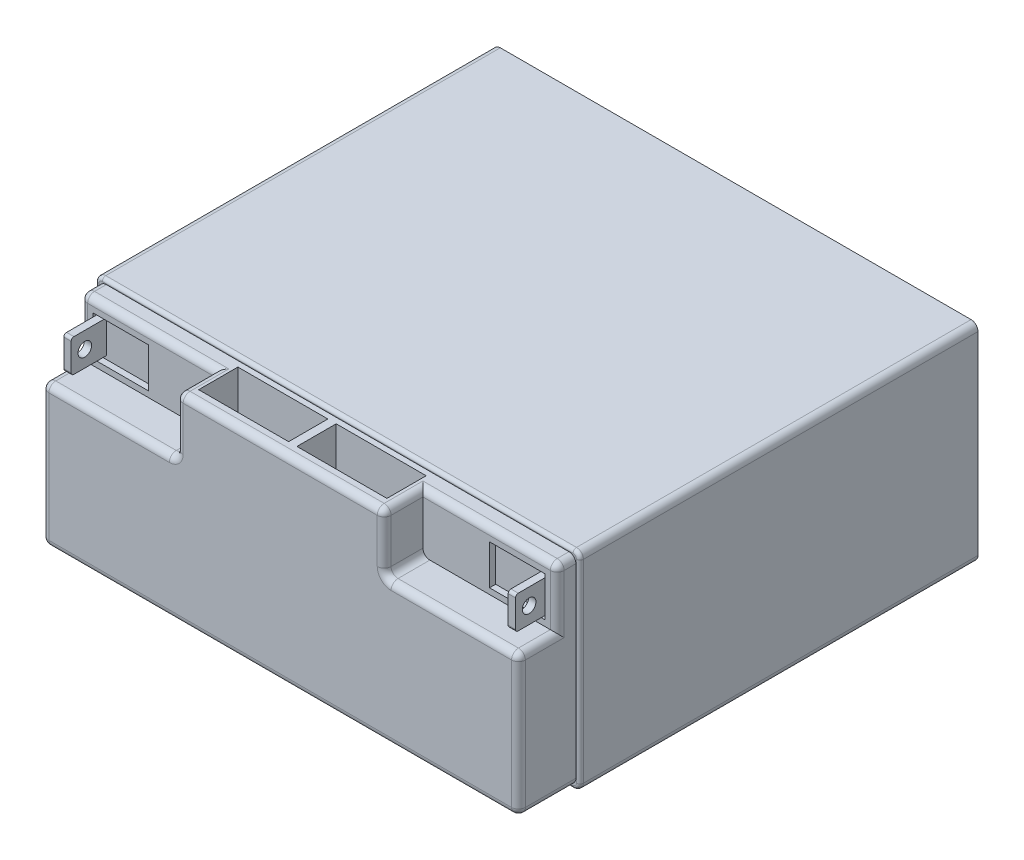
SolidWorks part; units mm, degrees
ref_plane "Front Plane" through (0, 0, 0) normal (0, 0, 1) x (1, 0, 0)
ref_plane "Top Plane" through (0, 0, 0) normal (0, 1, 0) x (1, 0, 0)
ref_plane "Right Plane" through (0, 0, 0) normal (1, 0, 0) x (0, 0, -1)
ref_plane "Plane1" through (0, -62.2132, 0) normal (0, -1, 0) x (1, 0, 0)
sketch "Sketch1" plane through (0, -62.2132, 0) normal (0, -1, 0) x (1, 0, 0)
  line L0 (-33.1131, 0) -> (144.6869, 0)
  line L1 (144.6869, 0) -> (144.6869, 146.05)
  line L2 (144.6869, 146.05) -> (-33.1131, 146.05)
  line L3 (-33.1131, 146.05) -> (-33.1131, 0)
extrude "Boss-Extrude1" add sketch "Sketch1" against normal blind 76.2
sketch "Sketch2" plane through (0, 0, 146.05) normal (0, 0, 1) x (1, 0, 0)
  line L0 (143.2096, -60.7358) -> (-31.6357, -60.7358)
  line L1 (-31.6357, -60.7358) -> (-31.6357, 12.5094)
  line L2 (-31.6357, 12.5094) -> (143.2096, 12.5094)
  line L3 (143.2096, 12.5094) -> (143.2096, -60.7358)
extrude "Boss-Extrude2" add sketch "Sketch2" along normal blind 21.082
sketch "Sketch3" plane through (-31.6357, 0, 0) normal (-1, 0, 0) x (0, 0, 1)
  line L0 (152.908, 12.5094) -> (152.908, -8.8266)
  line L1 (152.908, -8.8266) -> (167.132, -8.8266)
  line L2 (167.132, -8.8266) -> (167.132, 12.5094)
  line L3 (167.132, 12.5094) -> (152.908, 12.5094)
extrude "Cut-Extrude1" cut sketch "Sketch3" against normal blind 49.276
sketch "Sketch4" plane through (0, 0, 152.908) normal (0, 0, 1) x (1, 0, 0)
  line L0 (-24.3791, -5.3674) -> (-27.0726, -5.3674)
  line L1 (-27.0726, -5.3674) -> (-27.0726, 6.6326)
  line L2 (-27.0726, 6.6326) -> (-24.3791, 6.6326)
  line L3 (-24.3791, 6.6326) -> (-24.3791, -5.3674)
extrude "Boss-Extrude3" add sketch "Sketch4" along normal blind 10.746
sketch "Sketch5" plane through (0, 0, 152.908) normal (0, 0, 1) x (1, 0, 0)
  line L0 (-27.0726, 6.6326) -> (-24.3791, 6.6326)
  line L1 (-24.3791, 6.6326) -> (-24.3791, -5.3674)
  line L2 (-24.3791, -5.3674) -> (-27.0726, -5.3674)
  line L3 (-27.0726, -5.3674) -> (-27.0726, -6.6776)
  line L4 (-27.0726, -6.6776) -> (-6.7872, -6.6776)
  line L5 (-6.7872, -6.6776) -> (-6.7872, 7.9428)
  line L6 (-6.7872, 7.9428) -> (-27.0726, 7.9428)
  line L7 (-27.0726, 7.9428) -> (-27.0726, 6.6326)
extrude "Cut-Extrude2" cut sketch "Sketch5" against normal blind 2.254
sketch "Sketch6" plane through (0, 12.5094, 0) normal (0, 1, 0) x (-1, 0, 0)
  line L0 (-143.2096, 152.908) -> (-93.9336, 152.908)
  line L1 (-93.9336, 152.908) -> (-93.9336, 167.132)
  line L2 (-93.9336, 167.132) -> (-143.2096, 167.132)
  line L3 (-143.2096, 167.132) -> (-143.2096, 152.908)
extrude "Cut-Extrude3" cut sketch "Sketch6" against normal blind 21.336
sketch "Sketch7" plane through (0, 0, 152.908) normal (0, 0, 1) x (1, 0, 0)
  line L0 (138.6465, -5.3674) -> (135.9529, -5.3674)
  line L1 (135.9529, -5.3674) -> (135.9529, 6.6326)
  line L2 (135.9529, 6.6326) -> (138.6465, 6.6326)
  line L3 (138.6465, 6.6326) -> (138.6465, -5.3674)
extrude "Boss-Extrude4" add sketch "Sketch7" along normal blind 10.746
sketch "Sketch8" plane through (0, 0, 152.908) normal (0, 0, 1) x (1, 0, 0)
  line L0 (138.6465, -5.3674) -> (135.9529, -5.3674)
  line L1 (135.9529, -5.3674) -> (135.9529, 6.6326)
  line L2 (135.9529, 6.6326) -> (138.6465, 6.6326)
  line L3 (138.6465, 6.6326) -> (138.6465, 7.9428)
  line L4 (138.6465, 7.9428) -> (118.361, 7.9428)
  line L5 (118.361, 7.9428) -> (118.361, -6.6776)
  line L6 (118.361, -6.6776) -> (138.6465, -6.6776)
  line L7 (138.6465, -6.6776) -> (138.6465, -5.3674)
extrude "Cut-Extrude4" cut sketch "Sketch8" against normal blind 2.254
sketch "Sketch9" plane through (0, 12.5094, 0) normal (0, 1, 0) x (-1, 0, 0)
  line L0 (-90.3309, 148.1138) -> (-57.3109, 148.1138)
  line L1 (-57.3109, 148.1138) -> (-57.3109, 162.5135)
  line L2 (-57.3109, 162.5135) -> (-90.3309, 162.5135)
  line L3 (-90.3309, 162.5135) -> (-90.3309, 148.1138)
extrude "Cut-Extrude5" cut sketch "Sketch9" against normal blind 19.05
sketch "Sketch10" plane through (0, 12.5094, 0) normal (0, 1, 0) x (-1, 0, 0)
  line L0 (-54.2629, 148.1138) -> (-21.2429, 148.1138)
  line L1 (-21.2429, 148.1138) -> (-21.2429, 162.5135)
  line L2 (-21.2429, 162.5135) -> (-54.2629, 162.5135)
  line L3 (-54.2629, 162.5135) -> (-54.2629, 148.1138)
extrude "Cut-Extrude6" cut sketch "Sketch10" against normal blind 19.05
sketch "Sketch11" plane through (0, -60.7358, 0) normal (0, -1, 0) x (1, 0, 0)
  line L0 (56.8496, 162.8434) -> (56.8496, 147.6421)
  line L1 (56.8496, 147.6421) -> (120.3496, 147.6421)
  line L2 (120.3496, 147.6421) -> (120.3496, 162.8434)
  line L3 (120.3496, 162.8434) -> (56.8496, 162.8434)
extrude "Cut-Extrude7" cut sketch "Sketch11" against normal blind 19.558
sketch "Sketch12" plane through (0, -60.7358, 0) normal (0, -1, 0) x (1, 0, 0)
  line L0 (-8.7757, 162.8434) -> (-8.7757, 147.6421)
  line L1 (-8.7757, 147.6421) -> (54.7243, 147.6421)
  line L2 (54.7243, 147.6421) -> (54.7243, 162.8434)
  line L3 (54.7243, 162.8434) -> (-8.7757, 162.8434)
extrude "Cut-Extrude8" cut sketch "Sketch12" against normal blind 19.558
hole_wizard "Ø5.0 (5) Diameter Hole1" positions "Sketch14" profile "Sketch13" hole size "Ø5.0" standard "ANSI Metric"
sketch "Sketch14" plane through (135.9529, 0, 0) normal (-1, 0, 0) x (0, 0, 1)
  point P0 (158.654, 0.6326)
sketch "Sketch13" plane through (135.9529, 0.6326, 158.654) normal (0, 1, 0) x (0, 0, 1)
  line L0 (0, 0) -> (0, 8.734)
  line L1 (0, 8.734) -> (2.5, 8.734)
  line L2 (2.5, 8.734) -> (2.5, 0)
  line L5 (2.5, 0) -> (0, 0)
  line L11 (0, -6.35) -> (0, 107.95) construction
  dimension "Thru Hole Dia." = 5
  dimension "Thru Hole Depth" = 8.734
hole_wizard "Ø5.0 (5) Diameter Hole2" positions "Sketch16" profile "Sketch15" hole size "Ø5.0" standard "ANSI Metric"
sketch "Sketch16" plane through (-24.3791, 0, 0) normal (1, 0, 0) x (0, 0, -1)
  point P0 (-158.654, 0.6326)
sketch "Sketch15" plane through (-24.3791, 0.6326, 158.654) normal (0, 1, 0) x (0, 0, -1)
  line L0 (0, 0) -> (0, 8.734)
  line L1 (0, 8.734) -> (2.5, 8.734)
  line L2 (2.5, 8.734) -> (2.5, 0)
  line L5 (2.5, 0) -> (0, 0)
  line L11 (0, -6.35) -> (0, 107.95) construction
  dimension "Thru Hole Dia." = 5
  dimension "Thru Hole Depth" = 8.734
fillet "Fillet1" radius 2.54 26 edges at (143.2096, -60.7358, 156.591) (143.2096, 1.8414, 152.908) (143.2096, 12.5094, 149.479) (-31.6357, -60.7358, 156.591) (55.7869, -60.7358, 167.132) (143.2096, -34.7812, 167.132) (143.2096, -8.8266, 160.02) (118.5716, 12.5094, 152.908) (-31.6357, 12.5094, 149.479) (-31.6357, 1.8414, 152.908) (-31.6357, -8.8266, 160.02) (-31.6357, -34.7812, 167.132) (93.9336, 1.8414, 167.132) (118.5716, -8.8266, 167.132) (93.9336, 12.5094, 160.02) (-6.9977, 12.5094, 152.908) (-6.9977, -8.8266, 167.132) (17.6403, 1.8414, 167.132) (55.7869, 12.5094, 167.132) (17.6403, 12.5094, 160.02) (17.6403, -8.8266, 160.02) (-33.1131, 13.9868, 73.025) (93.9336, -8.8266, 160.02) (144.6869, -62.2132, 73.025) (-33.1131, -62.2132, 73.025) (144.6869, 13.9868, 73.025) tangent propagation no
fillet "Fillet2" radius 1 4 edges at (-25.7258, -5.3674, 163.654) (-25.7258, 6.6326, 163.654) (137.2997, 6.6326, 163.654) (137.2997, -5.3674, 163.654) tangent propagation no
fillet "Fillet3" radius 1.27 8 edges at (-33.1131, -24.1132, 146.05) (-32.3691, 13.2428, 146.05) (-32.3691, -61.4693, 146.05) (55.7869, 13.9868, 146.05) (55.7869, -62.2132, 146.05) (143.943, 13.2428, 146.05) (143.943, -61.4693, 146.05) (144.6869, -24.1132, 146.05) tangent propagation no
